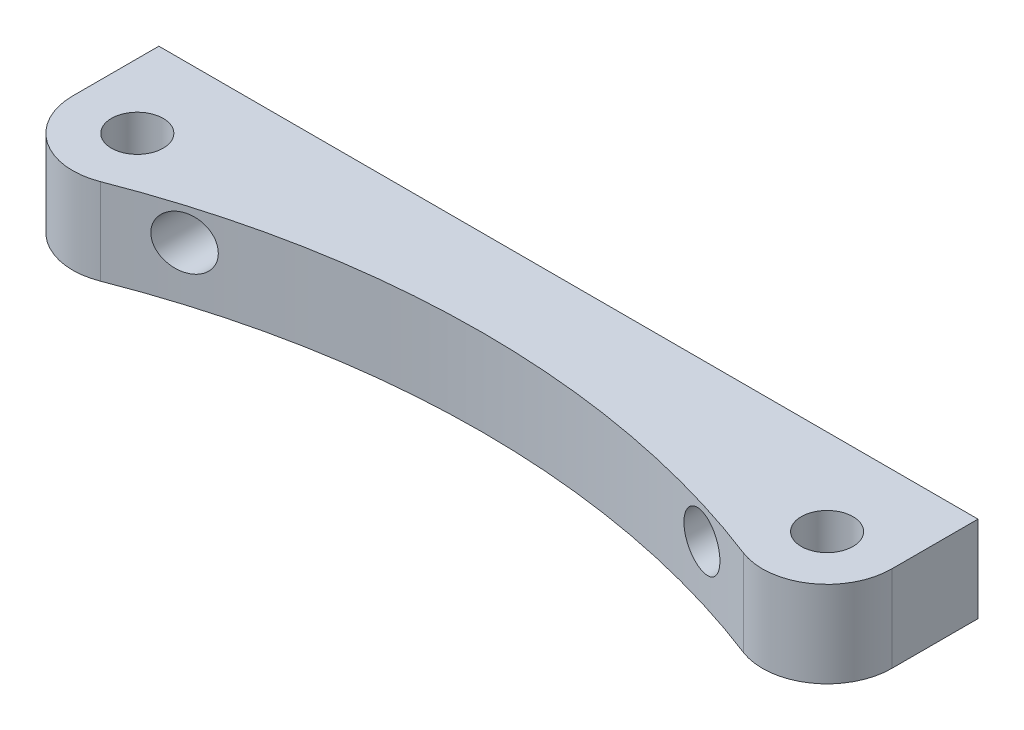
SolidWorks part; units mm, degrees
ref_plane "Front Plane" through (0, 0, 0) normal (0, 0, 1) x (1, 0, 0)
ref_plane "Top Plane" through (0, 0, 0) normal (0, 1, 0) x (1, 0, 0)
ref_plane "Right Plane" through (0, 0, 0) normal (1, 0, 0) x (0, 0, -1)
sketch "Sketch1" plane through (0, 0, 0) normal (0, 1, 0) x (1, 0, 0)
  line L0 (0, 0) -> (50.8, 0) construction
  line L4 (-4.7625, 6.35) -> (-4.7625, 0)
  line L5 (55.5625, 0) -> (55.5625, 6.35)
  line L7 (-4.7625, 6.35) -> (55.5625, 6.35)
  arc A0 (-4.7625, 0) -> (1.7253, -4.439) centre (0, 0) ccw
  arc A1 (49.0747, -4.439) -> (55.5625, 0) centre (50.8, 0) ccw
  circle A2 centre (0, 0) radius 1.905
  circle A3 centre (50.8, 0) radius 1.905
  arc A4 (1.7253, -4.439) -> (49.0747, -4.439) centre (25.4, -65.3521) cw
  point P3 (25.4, 0)
  dimension "D3" = 3.81
  dimension "D4" = 4.7625
  dimension "D1" = 6.35
  dimension "D2" = 50.8
  dimension "D5" = 6.35
extrude "Boss-Extrude1" add sketch "Sketch1" along normal blind 6.35
sketch "Sketch2" plane through (0, 0, -6.35) normal (0, 0, -1) x (-1, 0, 0)
  circle A0 centre (-44.45, 3.9688) radius 1.905
  arc A1 (-41.2, 3.9688) -> (-47.7, 3.9688) centre (-44.45, 3.9688) ccw construction
  circle A2 centre (-6.35, 3.9688) radius 1.905
  arc A3 (-3.1, 3.9688) -> (-9.6, 3.9688) centre (-6.35, 3.9688) ccw construction
  dimension "D1" = 3.81
extrude "Cut-Extrude1" cut sketch "Sketch2" against normal up to next
